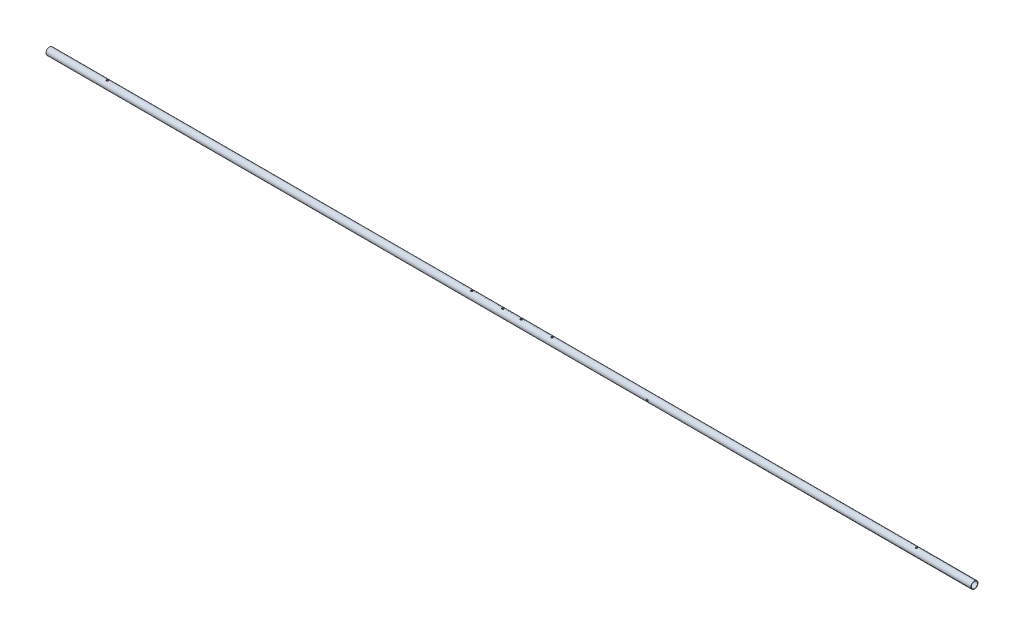
SolidWorks part; units mm, degrees
material "Galvanized Steel"
ref_plane "Front Plane" through (0, 0, 0) normal (0, 0, 1) x (1, 0, 0)
ref_plane "Top Plane" through (0, 0, 0) normal (0, 1, 0) x (1, 0, 0)
ref_plane "Right Plane" through (0, 0, 0) normal (1, 0, 0) x (0, 0, -1)
sketch "Sketch3" plane through (0, 0, 0) normal (1, 0, 0) x (0, 0, -1)
  circle A0 centre (0, 0) radius 10.4648
  circle A1 centre (0, 0) radius 11.7094
  dimension "D1" = 20.9296
  dimension "D2" = 23.4188
extrude "Boss-Extrude1" add sketch "Sketch3" along normal blind 3048
sketch "Sketch4" plane through (0, 0, 0) normal (0, 1, 0) x (1, 0, 0)
  line L0 (0, 11.7094) -> (0, -11.7094) construction
  circle A0 centre (1493.52, 0) radius 3.175
  circle A1 centre (1554.48, 0) radius 3.175
  circle A2 centre (1656.1816, 0) radius 3.175
  circle A3 centre (1391.8184, 0) radius 3.175
  point P0 (1524, 0)
  point P1 (1554.48, 0)
  point P3 (1493.52, 0)
  dimension "D4" = 6.35
  dimension "D5" = 6.35
  dimension "D6" = 132.1816
  dimension "D1" = 1524
  dimension "D2" = 30.48
  dimension "D3" = 30.48
  dimension "D7" = 132.1816
extrude "Cut-Extrude1" cut sketch "Sketch4" against normal through all and the other way through all
sketch "Sketch5" plane through (0, 0, 0) normal (0, 1, 0) x (1, 0, 0)
  line L0 (3048, -11.7094) -> (3048, 11.7094) construction
  circle A0 centre (190.5, 0) radius 3.175
  circle A1 centre (2857.5, 0) radius 3.175
  point P0 (190.5, 0)
  point P4 (2857.5, 0)
  dimension "D2" = 6.35
  dimension "D4" = 6.35
  dimension "D1" = 190.5
  dimension "D3" = 190.5
extrude "Cut-Extrude2" cut sketch "Sketch5" against normal through all and the other way through all
sketch "Sketch7" plane through (0, 0, 0) normal (0, 0, 1) x (1, 0, 0)
  circle A0 centre (1981.2, 0) radius 3.175
  point P2 (1524, 0)
  dimension "D1" = 1524
  dimension "D2" = 457.2
extrude "Cut-Extrude3" cut sketch "Sketch7" against normal through all and the other way through all
equation "\"extrudelength\"=120"
equation "\"D1@Boss-Extrude1\"=\"extrudelength\""
equation "\"D1@Sketch7\"=\"extrudelength\"/2"
equation "\"D1@Sketch4\"=\"extrudelength\"/2"
